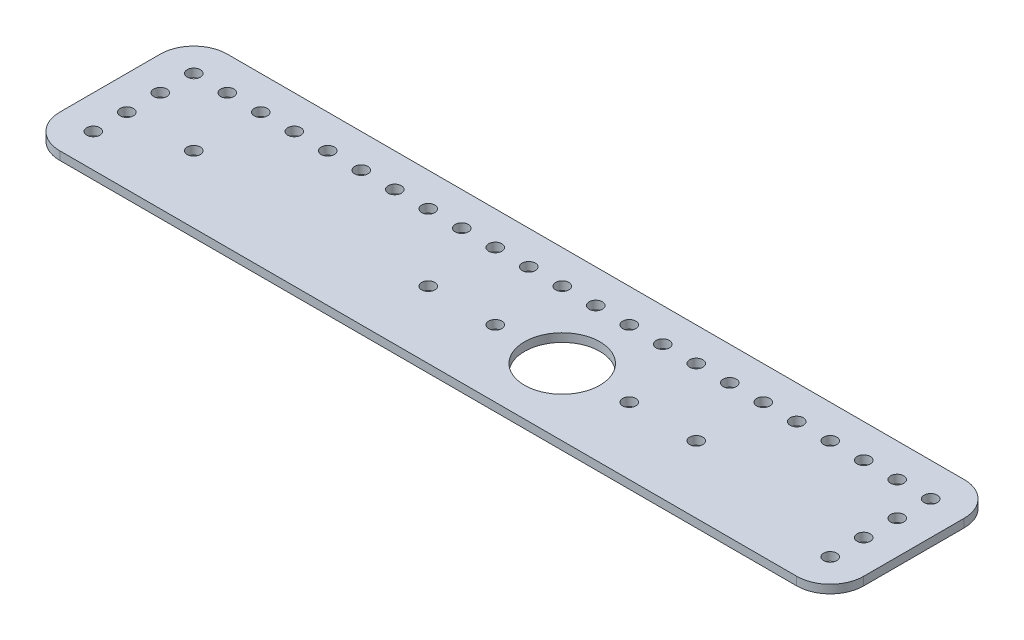
SolidWorks part; units mm, degrees
material "6061 Alloy"
ref_plane "Front Plane" through (0, 0, 0) normal (0, 0, 1) x (1, 0, 0)
ref_plane "Top Plane" through (0, 0, 0) normal (0, 1, 0) x (1, 0, 0)
ref_plane "Right Plane" through (0, 0, 0) normal (1, 0, 0) x (0, 0, -1)
sketch "Sketch1" plane through (0, 0, 0) normal (0, 1, 0) x (1, 0, 0)
  line L0 (0, 0) -> (0, 63.5)
  line L1 (0, 63.5) -> (304.8, 63.5)
  line L2 (304.8, 63.5) -> (304.8, 0)
  line L3 (304.8, 0) -> (279.4, 0)
  line L4 (279.4, 0) -> (279.4, 38.1)
  line L5 (279.4, 38.1) -> (25.4, 38.1)
  line L6 (25.4, 38.1) -> (25.4, 0)
  line L7 (25.4, 0) -> (0, 0)
  line L8 (12.7, 50.8) -> (25.4, 50.8) construction
  line L9 (12.7, 50.8) -> (12.7, 38.1) construction
  line L10 (25.4, 0) -> (279.4, 0)
  circle A0 centre (12.7, 50.8) radius 2.4892
  circle A1 centre (25.4, 50.8) radius 2.4892
  circle A2 centre (38.1, 50.8) radius 2.4892
  circle A3 centre (50.8, 50.8) radius 2.4892
  circle A4 centre (63.5, 50.8) radius 2.4892
  circle A5 centre (76.2, 50.8) radius 2.4892
  circle A6 centre (88.9, 50.8) radius 2.4892
  circle A7 centre (101.6, 50.8) radius 2.4892
  circle A8 centre (114.3, 50.8) radius 2.4892
  circle A9 centre (127, 50.8) radius 2.4892
  circle A10 centre (139.7, 50.8) radius 2.4892
  circle A11 centre (152.4, 50.8) radius 2.4892
  circle A12 centre (165.1, 50.8) radius 2.4892
  circle A13 centre (177.8, 50.8) radius 2.4892
  circle A14 centre (190.5, 50.8) radius 2.4892
  circle A15 centre (203.2, 50.8) radius 2.4892
  circle A16 centre (215.9, 50.8) radius 2.4892
  circle A17 centre (228.6, 50.8) radius 2.4892
  circle A18 centre (241.3, 50.8) radius 2.4892
  circle A19 centre (254, 50.8) radius 2.4892
  circle A20 centre (266.7, 50.8) radius 2.4892
  circle A21 centre (279.4, 50.8) radius 2.4892
  circle A22 centre (292.1, 50.8) radius 2.4892
  circle A23 centre (12.7, 38.1) radius 2.4892
  circle A24 centre (292.1, 38.1) radius 2.4892
  circle A25 centre (12.7, 25.4) radius 2.4892
  circle A26 centre (292.1, 25.4) radius 2.4892
  circle A27 centre (12.7, 12.7) radius 2.4892
  circle A28 centre (292.1, 12.7) radius 2.4892
  dimension "D6" = 12.7
  dimension "D7" = 12.7
  dimension "D8" = 4.9784
  dimension "D1" = 25.4
  dimension "D2" = 304.8
  dimension "D3" = 25.4
  dimension "D4" = 25.4
  dimension "D5" = 63.5
  dimension "D10" = 12.7
  dimension "D12" = 12.7
  dimension "D9" = 23
  dimension "D11" = 4
extrude "Boss-Extrude1" add sketch "Sketch1" along normal blind 3.175 contours L6 L10 L4 L5 | L7 L6 L5 L4 L3 L2 L1 L0 A28 A27 A26 A25 A24 A23 A22 A21 A20 A19 A18 A17 A16 A15 A14 region at (152.4, 0, -44.3822) region at (152.4, 0, -19.05)
sketch "Sketch2" plane through (0, 3.175, 0) normal (0, 1, 0) x (1, 0, 0)
  line B0 (68.7873, 5.0409) -> (202.7488, 5.0409)
  line B1 (202.7488, 74.8909) -> (68.7873, 74.8909)
  circle B2 centre (237.8973, 39.9659) radius 2.54
  circle B3 centre (221.6286, 39.9659) radius 2.54
  arc B4 (216.9621, 58.6686) -> (222.2457, 55.8409) centre (222.2457, 62.1909) ccw
  arc B5 (68.7873, 74.8909) -> (63.5038, 72.0633) centre (68.7873, 68.5409) ccw
  arc B6 (47.3973, 62.1909) -> (41.0473, 55.8409) centre (47.3973, 55.8409) ccw
  circle B7 centre (187.0973, 39.9659) radius 14.2875
  circle B8 centre (152.5659, 39.9659) radius 2.54
  circle B9 centre (107.7223, 62.1909) radius 2.4892
  circle B10 centre (136.2973, 39.9659) radius 2.54
  circle B11 centre (107.7223, 17.7409) radius 2.4892
  circle B12 centre (69.6223, 17.7409) radius 2.4892
  circle B13 centre (47.3973, 39.9659) radius 2.54
  circle B14 centre (69.6223, 62.1909) radius 2.4892
sketch_block_instance "Block-new elevator gusset-1"
sketch_block "Block-new elevator gusset"
sketch "Sketch3" plane through (0, 3.175, 0) normal (0, 1, 0) x (1, 0, 0)
  line L0 (304.8, 63.5) -> (304.8, 0) construction
  line L2 (0, 63.5) -> (304.8, 63.5) construction
  circle A0 centre (60.3142, 47.625) radius 2.4892 construction
  circle A1 centre (98.4142, 47.625) radius 2.4892 construction
  circle A2 centre (126.9892, 25.4) radius 2.4892
  circle A3 centre (143.2579, 25.4) radius 2.4892 construction
  circle A4 centre (177.7892, 25.4) radius 14.2875
  circle A5 centre (212.3206, 25.4) radius 2.4892 construction
  circle A6 centre (228.5892, 25.4) radius 2.4892
  circle A7 centre (98.4142, 3.175) radius 2.4892 construction
  circle A8 centre (60.3142, 3.175) radius 2.4892 construction
  circle A9 centre (38.0892, 25.4) radius 2.4892
  circle A10 centre (152.3892, 25.4) radius 2.4892
  circle A11 centre (203.1892, 25.4) radius 2.4892
  dimension "D1" = 28.575
  dimension "D2" = 4.9784
  dimension "D3" = 44.45
  dimension "D4" = 38.1
  dimension "D5" = 22.225
  dimension "D6" = 16.2686
  dimension "D7" = 16.2686
  dimension "D8" = 34.5314
  dimension "D9" = 34.5314
  dimension "D10" = 28.575
  dimension "D11" = 22.225
  dimension "D12" = 127.0108
  dimension "D13" = 38.1
  dimension "D14" = 25.4
  dimension "D15" = 25.4
extrude "Cut-Extrude1" cut sketch "Sketch3" against normal through all
fillet "Fillet1" radius 12.7 4 edges at (0, 1.5875, -63.5) (304.8, 1.5875, -63.5) (304.8, 1.5875, 0) (0, 1.5875, 0)
sketch "Sketch4" plane through (0, 3.175, 0) normal (0, -1, 0) x (1, 0, 0)
  line L0 (-1033.1809, 0) -> (48966.8191, 0) construction
  line L1 (0, -968.3084) -> (0, 49031.6916) construction
  point P3 (0, 0)
